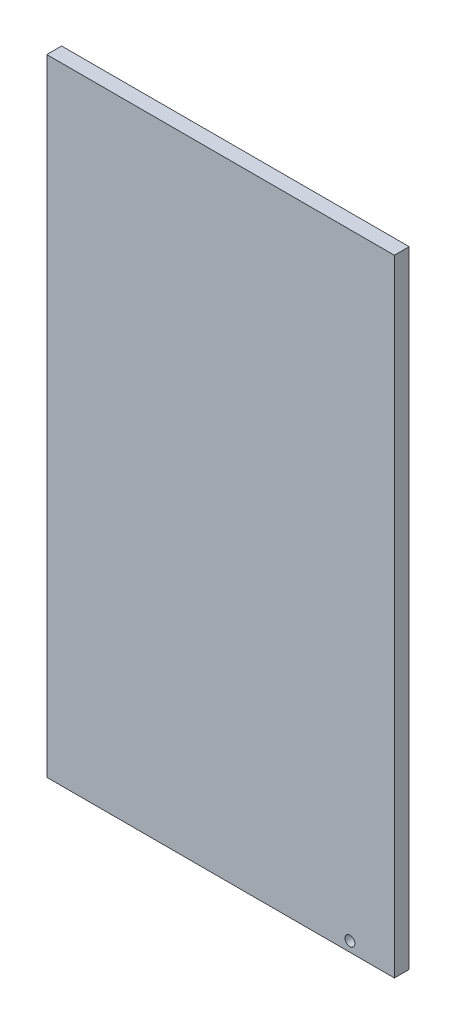
SolidWorks part; units mm, degrees
material "Perspex (TM) GS Acrylic Cast Sheet"
ref_plane "Front Plane" through (0, 0, 0) normal (0, 0, 1) x (1, 0, 0)
ref_plane "Top Plane" through (0, 0, 0) normal (0, 1, 0) x (1, 0, 0)
ref_plane "Right Plane" through (0, 0, 0) normal (1, 0, 0) x (0, 0, -1)
sketch "Sketch1" plane through (0, 0, 0) normal (0, 0, 1) x (1, 0, 0)
  line L1 (-105.5, -190) -> (105.5, -190)
  line L2 (-105.5, -190) -> (-105.5, 190)
  line L3 (-105.5, 190) -> (105.5, 190)
  line L4 (105.5, -190) -> (105.5, 190)
  line L5 (-105.5, -190) -> (105.5, 190) construction
  line L6 (-105.5, 190) -> (105.5, -190) construction
  point P0 (0, 0)
  dimension "D1" = 211
  dimension "D2" = 380
extrude "Boss-Extrude1" add sketch "Sketch1" along normal blind 9
sketch "Sketch2" plane through (0, 0, 9) normal (0, 0, 1) x (1, 0, 0)
  line L0 (105.5, -190) -> (105.5, 190) construction
  line L1 (-105.5, -190) -> (105.5, -190) construction
  circle A0 centre (78.5, -184) radius 3
  dimension "D1" = 6
  dimension "D2" = 27
  dimension "D3" = 6
extrude "Cut-Extrude1" cut sketch "Sketch2" against normal through all
equation "\"PCLength\"= 150mm'Length across I/O from PS to GPU"
equation "\"PCWidth\"= 340mm'Distance of longest part parallel to GPU(ussually GPU)"
equation "\"PCHeight\"= 190mm'Tallest point with mobo laying flat"
equation "\"WallThickness\"= 9mm'Thickness of each outer tank wall"
equation "\"ThermoBarrierThickness\"= 6mm'Thickness of barrier between hot side and cold side"
equation "\"HotSideGap\"= 15mm'Space in the hot side that hot fluid flows into"
equation "\"PCClearance\"= 40mm'Clearance from top of tank to top of PC"
equation "\"RadiatorHeight\"= 277.37mm'Final Height from ground of radiators"
equation "\"D1@Sketch1\"=\"PCHeight\" + \"ThermoBarrierThickness\" + \"HotSideGap\""
equation "\"D2@Sketch1\"=\"PCWidth\" + \"PCClearance\""
equation "\"D1@Boss-Extrude1\"=\"WallThickness\""
equation "\"D2@Sketch2\"=\"HotSideGap\" + \"ThermoBarrierThickness\" + 6"
